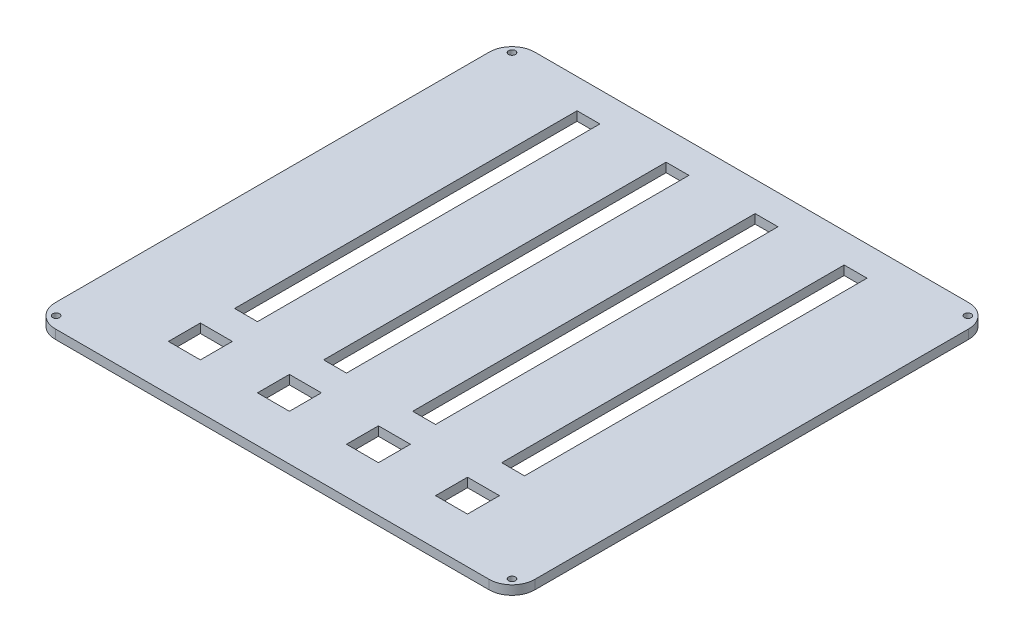
SolidWorks part; units mm, degrees
ref_plane "Front Plane" through (0, 0, 0) normal (0, 0, 1) x (1, 0, 0)
ref_plane "Top Plane" through (0, 0, 0) normal (0, 1, 0) x (1, 0, 0)
ref_plane "Right Plane" through (0, 0, 0) normal (1, 0, 0) x (0, 0, -1)
sketch "Sketch1" plane through (0, 0, 0) normal (0, 1, 0) x (1, 0, 0)
  line L0 (-101, -101) -> (-101, 101)
  line L5 (-105, -105) -> (105, -105)
  line L6 (-105, -105) -> (-105, 105)
  line L7 (-105, 105) -> (105, 105)
  line L8 (105, -105) -> (105, 105)
  line L9 (-101, 101) -> (101, 101)
  line L10 (101, -101) -> (101, 101)
  line L11 (-101, -101) -> (101, -101)
  line L12 (-101, 101) -> (-99.8333, 99.8333) construction
  line L13 (-55, 0) -> (55, 0) construction
  line L14 (-101, -101) -> (-99.8333, -99.8333) construction
  line L15 (0, -55) -> (0, 55) construction
  line L16 (101, -101) -> (99.8333, -99.8333) construction
  line L17 (101, 101) -> (99.8333, 99.8333) construction
  circle A1 centre (-99.8333, 99.8333) radius 1.5
  circle A2 centre (-99.8333, -99.8333) radius 1.5
  circle A3 centre (99.8333, -99.8333) radius 1.5
  circle A4 centre (99.8333, 99.8333) radius 1.5
  point P0 (0, 0)
  point P6 (-105, 0)
  point P7 (0, 105)
  dimension "D3" = 4
  dimension "D4" = 3
  dimension "D1" = 210
  dimension "D2" = 210
  dimension "D5" = 1.65
  dimension "D6" = 45
extrude "MainExtrude" add sketch "Sketch1" along normal blind 4 contours L6 L5 L8 L7
extrude "ScrewHoles" cut sketch "Sketch1<6>" along normal up to surface (4 mm away) contours A1 | A2 | A3 | A4 up to face at (0, 4, 0)
sketch "Sketch1<6>" plane through (0, 0, 0) normal (0, 1, 0) x (1, 0, 0) same geometry as "Sketch1"
fillet "RoundedCorners" radius 10 4 edges at (-105, 2, -105) (-105, 2, 105) (105, 2, -105) (105, 2, 105)
sketch "Sketch2" plane through (0, 0, 0) normal (0, -1, 0) x (1, 0, 0)
  line L0 (-17.92, 37.135) -> (17.92, 37.135) construction
  line L1 (2.2, 0) -> (-2.2, 0) construction
  circle A0 centre (-17.92, 37.135) radius 0.98
  circle A1 centre (-17.92, 37.135) radius 2
  circle A2 centre (17.92, 37.135) radius 2
  circle A3 centre (17.92, 37.135) radius 0.98
  circle A4 centre (-17.92, -37.135) radius 0.98
  circle A5 centre (-17.92, -37.135) radius 2
  circle A6 centre (17.92, -37.135) radius 0.98
  circle A7 centre (17.92, -37.135) radius 2
  point P3 (0, 37.135)
  dimension "D1" = 1.96
  dimension "D2" = 4
  dimension "D4" = 37.135
  dimension "D5" = 35.84
  dimension "D6" = 74.27
  dimension "D3" = 2
extrude "PCBHoles" [suppressed] add sketch "Sketch2" along normal blind 2
fillet "PCBRounds" [suppressed] radius 2
sketch "Sketch3" plane through (0, 4, 0) normal (0, 1, 0) x (1, 0, 0)
  line L0 (-105, -95) -> (-105, 95) construction
  line L1 (-65.5, -85) -> (-51.5, -85)
  line L2 (-65.5, -85) -> (-65.5, -71)
  line L3 (-65.5, -71) -> (-51.5, -71)
  line L4 (-51.5, -85) -> (-51.5, -71)
  line L5 (-65.5, -85) -> (-51.5, -71) construction
  line L6 (-65.5, -71) -> (-51.5, -85) construction
  line L7 (-95, -105) -> (95, -105) construction
  line L8 (-26.5, -85) -> (-26.5, -71)
  line L9 (-26.5, -85) -> (-12.5, -85)
  line L10 (-12.5, -85) -> (-12.5, -71)
  line L11 (-26.5, -71) -> (-12.5, -71)
  line L12 (12.5, -85) -> (12.5, -71)
  line L13 (12.5, -85) -> (26.5, -85)
  line L14 (26.5, -85) -> (26.5, -71)
  line L15 (12.5, -71) -> (26.5, -71)
  line L16 (51.5, -85) -> (51.5, -71)
  line L17 (51.5, -85) -> (65.5, -85)
  line L18 (65.5, -85) -> (65.5, -71)
  line L19 (51.5, -71) -> (65.5, -71)
  line L20 (105, -95) -> (105, 95) construction
  line L21 (-24.5, 92) -> (-24.5, -58)
  line L22 (-63.5, 92) -> (-53.5, 92)
  line L23 (-63.5, 92) -> (-63.5, -58)
  line L24 (-63.5, -58) -> (-53.5, -58)
  line L25 (-53.5, 92) -> (-53.5, -58)
  line L26 (-63.5, 92) -> (-53.5, -58) construction
  line L27 (-63.5, -58) -> (-53.5, 92) construction
  line L28 (-24.5, 92) -> (-14.5, 92)
  line L29 (-14.5, 92) -> (-14.5, -58)
  line L30 (-24.5, -58) -> (-14.5, -58)
  line L31 (-24.5, -58) -> (-14.5, 92) construction
  line L32 (-24.5, 92) -> (-14.5, -58) construction
  line L33 (14.5, 92) -> (14.5, -58)
  line L34 (14.5, 92) -> (24.5, 92)
  line L35 (24.5, 92) -> (24.5, -58)
  line L36 (14.5, -58) -> (24.5, -58)
  line L37 (14.5, -58) -> (24.5, 92) construction
  line L38 (14.5, 92) -> (24.5, -58) construction
  line L39 (53.5, 92) -> (53.5, -58)
  line L40 (53.5, 92) -> (63.5, 92)
  line L41 (63.5, 92) -> (63.5, -58)
  line L42 (53.5, -58) -> (63.5, -58)
  line L43 (53.5, -58) -> (63.5, 92) construction
  line L44 (53.5, 92) -> (63.5, -58) construction
  line L45 (-26.5, -71) -> (-12.5, -85)
  line L46 (12.5, -71) -> (26.5, -85)
  line L47 (51.5, -71) -> (65.5, -85)
  line L49 (-70, 98) -> (70, 98) construction
  line L50 (-70, 98) -> (-70, -62) construction
  line L51 (-70, -62) -> (70, -62) construction
  line L52 (70, 98) -> (70, -62) construction
  line L53 (-70, 98) -> (70, -62) construction
  line L54 (-70, -62) -> (70, 98) construction
  point P0 (-58.5, -78)
  point P23 (-58.5, 17)
  point P29 (-19.5, 17)
  point P35 (19.5, 17)
  point P40 (58.5, 17)
  point P45 (-19.5, -78)
  point P46 (19.5, -78)
  point P47 (58.5, -78)
  dimension "D1" = 14
  dimension "D2" = 39.5
  dimension "D3" = 20
  dimension "D5" = 39.5
  dimension "D6" = 150
  dimension "D7" = 10
  dimension "D8" = 95
  dimension "D9" = 4
  dimension "D10" = 160
  dimension "D11" = 140
  dimension "D12" = 6.5
  dimension "D13" = 4
  dimension "D4" = 4
extrude "Cutouts" cut sketch "Sketch3" against normal blind 10 contours L23 L22 L25 L24 | L21 L30 L29 L28 | L33 L36 L35 L34 | L39 L42 L41 L40 | L2 L1 L4 L3 | L8 L11 L10 L9 | L12 L15 L14 L13 | L16 L19 L18 L17
sketch "Sketch4" plane through (0, 0, 0) normal (0, -1, 0) x (1, 0, 0)
  circle A0 centre (-70, 62) radius 1.25
  circle A1 centre (70, 62) radius 1.25
  circle A2 centre (70, -98) radius 1.25
  circle A3 centre (-70, -98) radius 1.25
  dimension "D1" = 2.5
sketch "Sketch5" plane through (0, 4, 0) normal (0, 1, 0) x (1, 0, 0)
  line L1 (-102.1071, -17.908) -> (-66.2671, -17.908) construction
  line L2 (-102.1071, -17.908) -> (-102.1071, -92.178) construction
  line L3 (-102.1071, -92.178) -> (-66.2671, -92.178) construction
  line L4 (-66.2671, -17.908) -> (-66.2671, -92.178) construction
  circle A0 centre (-102.1071, -17.908) radius 2
  circle A1 centre (-102.1071, -17.908) radius 0.98
  circle A2 centre (-66.2671, -17.908) radius 2
  circle A3 centre (-66.2671, -17.908) radius 0.98
  circle A4 centre (-66.2671, -92.178) radius 2
  circle A5 centre (-66.2671, -92.178) radius 0.98
  circle A6 centre (-102.1071, -92.178) radius 2
  circle A7 centre (-102.1071, -92.178) radius 0.98
  dimension "D3" = 4
  dimension "D4" = 1.96
  dimension "D1" = 35.84
  dimension "D2" = 74.27
extrude "Boss-Extrude1" [suppressed] add sketch "Sketch5" against normal blind 8
fillet "Fillet1" [suppressed] radius 0.5
